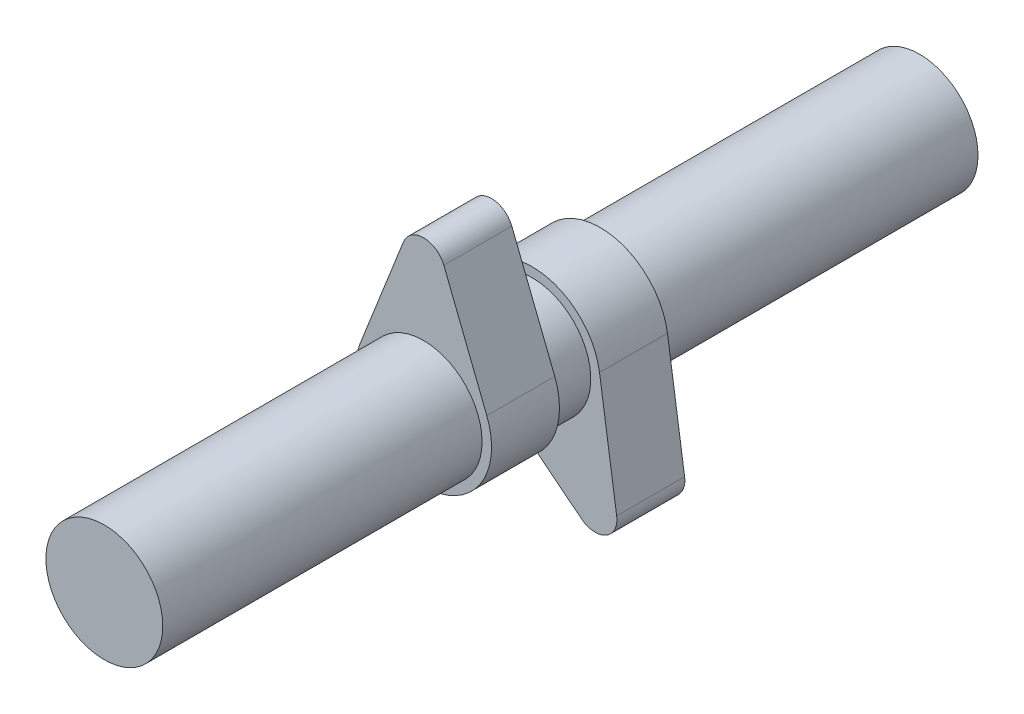
SolidWorks part; units mm, degrees
ref_plane "Front Plane" through (0, 0, 0) normal (0, 0, 1) x (1, 0, 0)
ref_plane "Top Plane" through (0, 0, 0) normal (0, 1, 0) x (1, 0, 0)
ref_plane "Right Plane" through (0, 0, 0) normal (1, 0, 0) x (0, 0, -1)
sketch "Sketch2" plane through (0, 0, 0) normal (0, 0, 1) x (1, 0, 0)
  circle A0 centre (0, 0) radius 21.5
  dimension "D1" = 43
extrude "Boss-Extrude1" add sketch "Sketch2" along normal mid plane 300 contours A0
sketch "Sketch3" plane through (0, 0, 150) normal (0, 0, 1) x (1, 0, 0)
  line L3 (-23.2498, 9.1894) -> (-7.4399, 49.1894)
  line L4 (7.4399, 49.1894) -> (23.2498, 9.1894)
  arc A1 (-7.4399, 49.1894) -> (7.4399, 49.1894) centre (0, 46.2488) cw
  arc A3 (-23.2498, 9.1894) -> (23.2498, 9.1894) centre (0, 0) ccw
  circle M6 centre (0, 0) radius 21.5
  dimension "D1" = 8
  dimension "D2" = 25
  dimension "D3" = 40
extrude "Boss-Extrude2" add sketch "Sketch3" against normal mid plane 25 from offset 130 contours A1 M6 region at (-14.4734, 28.845, 150) offset against normal yes
sketch "Sketch4" plane through (0, 0, 150) normal (0, 0, 1) x (1, 0, 0)
  line L0 (24.7297, 3.6666) -> (31.0379, -38.8793)
  line L1 (18.1515, -46.3193) -> (-15.5402, -19.5832)
  line L2 (-23.2498, 9.1894) -> (-7.4399, 49.1894) construction
  line L3 (7.4399, 49.1894) -> (23.2498, 9.1894) construction
  line L4 (0, 0) -> (0, -25) construction
  line L5 (23.1244, -40.0526) -> (27.1244, -46.9808) construction
  arc A0 (31.0379, -38.8793) -> (18.1515, -46.3193) centre (23.1244, -40.0526) cw
  arc A1 (24.7297, 3.6666) -> (-15.5402, -19.5832) centre (0, 0) ccw
  arc A3 (-23.2498, 9.1894) -> (23.2498, 9.1894) centre (0, 0) ccw construction
  arc A4 (7.4399, 49.1894) -> (-7.4399, 49.1894) centre (0, 46.2488) ccw construction
  dimension "D1" = 150
extrude "Boss-Extrude3" add sketch "Sketch4" along normal mid plane 25 from offset 170 offset against normal yes
equation "\"Camshaft Radius\"= 43mm'CHANGE LATER"
equation "\"Lobe Radius\"= 25mm'CHANGLE LATER"
equation "\"D1@Sketch2\"=\"Camshaft Radius\""
equation "\"D2@Sketch3\"=\"Lobe Radius\""
